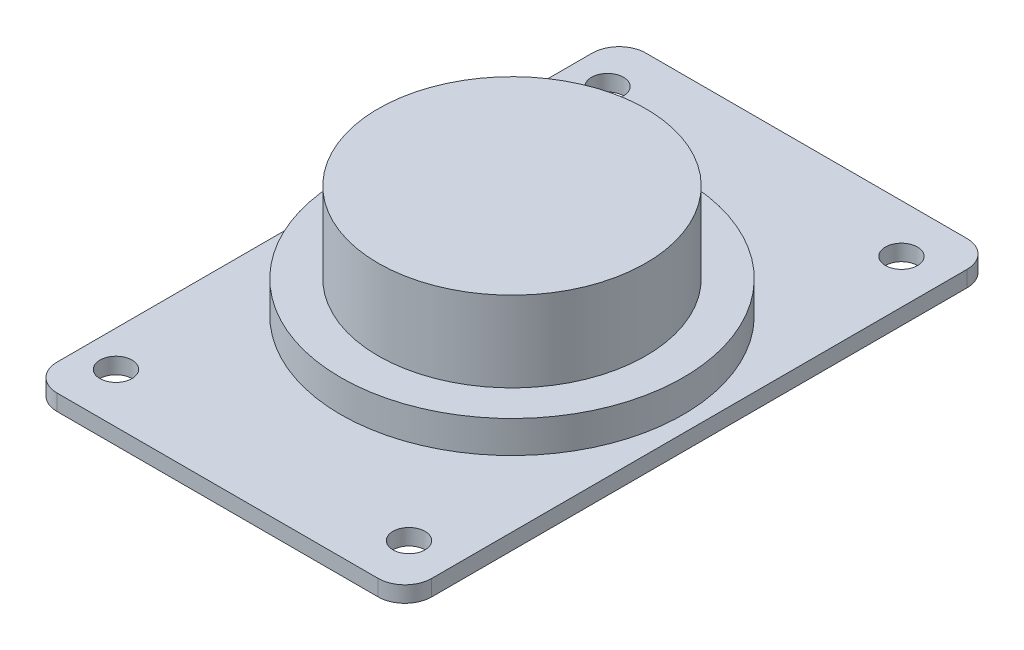
SolidWorks part; units mm, degrees
material "201 Annealed Stainless Steel (SS)"
ref_plane "Front Plane" through (0, 0, 0) normal (0, 0, 1) x (1, 0, 0)
ref_plane "Top Plane" through (0, 0, 0) normal (0, 1, 0) x (1, 0, 0)
ref_plane "Right Plane" through (0, 0, 0) normal (1, 0, 0) x (0, 0, -1)
sketch "Sketch3" plane through (0, 0, 0) normal (0, 1, 0) x (1, 0, 0)
  circle A0 centre (0, 0) radius 25
extrude "Boss-Extrude1" add sketch "Sketch3" against normal blind 15 contours A0
sketch "Sketch4" plane through (0, -15, 0) normal (0, -1, 0) x (1, 0, 0)
  circle A0 centre (0, 0) radius 32
extrude "Boss-Extrude2" add sketch "Sketch4" along normal blind 6
sketch "Sketch6" plane through (0, -21, 0) normal (0, -1, 0) x (1, 0, 0)
  line L1 (35, 0) -> (35, -55)
  line L2 (35, -55) -> (-35, -55)
  line L3 (-35, -55) -> (-35, 55)
  line L4 (-35, 55) -> (35, 55)
  line L5 (35, 55) -> (35, 0)
extrude "Boss-Extrude3" add sketch "Sketch6" along normal blind 3
fillet "Fillet1" radius 5 1 edges at (35, -22.5, 55)
fillet "Fillet2" radius 5 3 edges at (-35, -22.5, 55) (-35, -22.5, -55) (35, -22.5, -55)
sketch "Sketch8" plane through (0, -24, 0) normal (0, -1, 0) x (1, 0, 0)
  circle A0 centre (26.7585, -46) radius 3
  circle A1 centre (-28.159, -46) radius 3
  circle A2 centre (26.7585, 46) radius 3
  circle A3 centre (-28.3209, 45.6631) radius 3
extrude "Cut-Extrude1" cut sketch "Sketch8" against normal blind 3 contours A3 | A2 | A1 | A0
